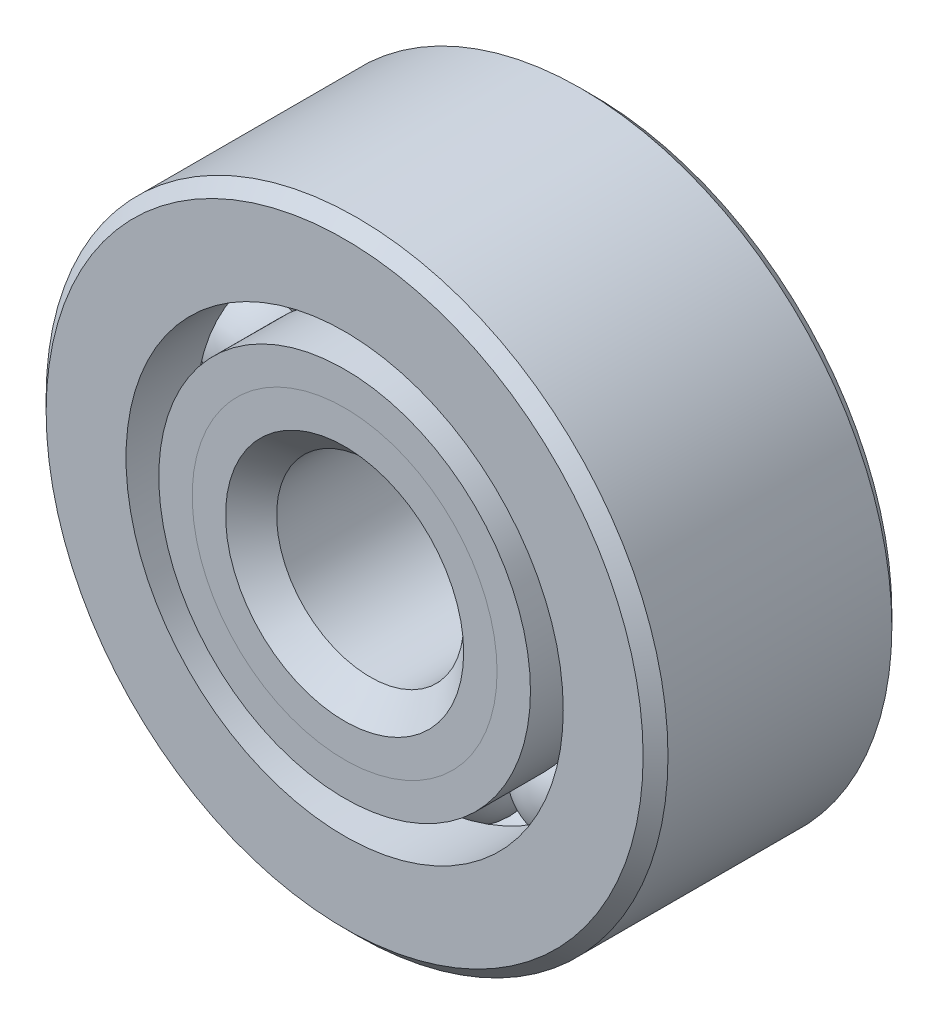
SolidWorks part; units mm, degrees
ref_plane "Front Plane" through (0, 0, 0) normal (0, 0, 1) x (1, 0, 0)
ref_plane "Top Plane" through (0, 0, 0) normal (0, 1, 0) x (1, 0, 0)
ref_plane "Right Plane" through (0, 0, 0) normal (1, 0, 0) x (0, 0, -1)
sketch "Sketch1" plane through (0, 0, 0) normal (1, 0, 0) x (0, 0, -1)
  line L0 (-0.7937, 0) -> (0.7937, 0) construction
  line L1 (0, 1.9844) -> (0, -1.9844) construction
  line L2 (0.7144, 1.9844) -> (-0.7144, 1.9844)
  line L3 (-0.7144, 1.9844) -> (-0.7938, 1.905)
  line L4 (-0.7938, 1.905) -> (-0.7938, 1.3953)
  line L5 (-0.7938, 1.3953) -> (-0.3528, 1.3953)
  line L6 (0.7938, 1.3953) -> (0.3528, 1.3953)
  line L7 (0.7938, 1.905) -> (0.7938, 1.3953)
  line L8 (0.7144, 1.9844) -> (0.7938, 1.905)
  line L9 (0, 1.9844) -> (0, 1.2906) construction
  line L10 (0, 1.2906) -> (0, 0.5969) construction
  arc A0 (-0.3528, 1.3953) -> (0.3528, 1.3953) centre (0, 1.2906) cw
  point P14 (0, 0.5969)
  dimension "Width" = 1.5875
  dimension "OD" = 3.9688
  dimension "D1" = 45
  dimension "D2" = 0.0794
  dimension "D3" = 0.7056
  dimension "D4" = 0.1047
revolve "Revolve1" add sketch "Sketch1" angle 360 about L0
sketch "Sketch2" plane through (0, 0, 0) normal (1, 0, 0) x (0, 0, -1)
  line L0 (-0.7938, 1.186) -> (-0.3528, 1.186)
  line L1 (-0.7938, 1.905) -> (-0.7938, -1.905) construction
  line L2 (-0.7938, 1.186) -> (-0.7938, 0.9729)
  line L3 (-0.7938, 0.9729) -> (-0.5807, 0.7598)
  line L4 (-0.5807, 0.7598) -> (0, 0.7598)
  line L5 (0, 1.9844) -> (0, -1.9844) construction
  line L6 (0, 0.7598) -> (0, 0.9227)
  line L7 (0, 0.9227) -> (0, 0.5969) construction
  line L8 (-0.7938, 1.186) -> (-0.7938, 0.7598) construction
  line L9 (-0.7938, 0.7598) -> (-0.5807, 0.7598) construction
  arc A0 (-0.3528, 1.186) -> (0, 0.9227) centre (0, 1.2906) ccw
  arc A1 (0.3528, 1.3953) -> (-0.3528, 1.3953) centre (0, 1.2906) ccw construction
  circle A2 centre (0, 1.2906) radius 0.368 construction
  dimension "D1" = 45
revolve "Revolve2" add sketch "Sketch2" angle 360 about L0
sketch "Sketch3" plane through (0, 0, 0) normal (1, 0, 0) x (0, 0, -1)
  line L0 (-0.7938, 0.9729) -> (-0.5807, 0.7598)
  line L1 (-0.5807, 0.7598) -> (0, 0.7598)
  line L2 (0, 0.7598) -> (0, 0.9227)
  line L3 (-0.7938, 0.9729) -> (-0.7938, 0.7598)
  line L4 (-0.7938, 1.186) -> (-0.7938, 0.7598) construction
  line L5 (-0.7938, 0.7598) -> (-0.6309, 0.5969)
  line L6 (-0.6309, 0.5969) -> (0.7144, 0.5969)
  line L7 (0.7144, 1.9844) -> (0.7144, -1.9844) construction
  line L8 (0.7144, 0.5969) -> (0.7938, 0.6763)
  line L9 (0.7938, -1.905) -> (0.7938, 1.905) construction
  line L10 (0.7938, 0.6763) -> (0.7938, 1.186)
  line L11 (0.7938, 1.186) -> (0.3528, 1.186)
  line L13 (0.7144, 1.9844) -> (0.7938, 1.905) construction
  circle A0 centre (0, 1.2906) radius 0.368 construction
  arc A1 (0.3528, 1.186) -> (0, 0.9227) centre (0, 1.2906) cw
revolve "Revolve3" add sketch "Sketch3" angle 360 about L0
sketch "Sketch4" plane through (0, 0, 0) normal (1, 0, 0) x (0, 0, -1)
  line L0 (-0.368, 1.2906) -> (0.368, 1.2906)
  circle A1 centre (0, 1.2906) radius 0.368 construction
  arc A2 (-0.368, 1.2906) -> (0.368, 1.2906) centre (0, 1.2906) cw
  arc A3 (0.3528, 1.3953) -> (-0.3528, 1.3953) centre (0, 1.2906) ccw construction
revolve "Revolve4" add sketch "Sketch4" angle 360 about L0
ref_axis "Axis1" through (0, 0, -0.7937) along (0, 0, 1)
pattern_circular "CirPattern1" count 10 every 36 about axis through (0, 0, -0.7937) along (0, 0, 1) of bodies 104
equation "\"D2@Sketch1\" = \"Width@Sketch1\"*.05"
equation "\"D3@Sketch1\" = \"Width@Sketch1\"/2.25"
equation "\"D4@Sketch1\" = (((\"OD@Sketch1\"-\"Width@Sketch1\")/2)/3.25)/3.5"
equation "\"D2@CirPattern1\" = 360/\"Balls@CirPattern1\""
